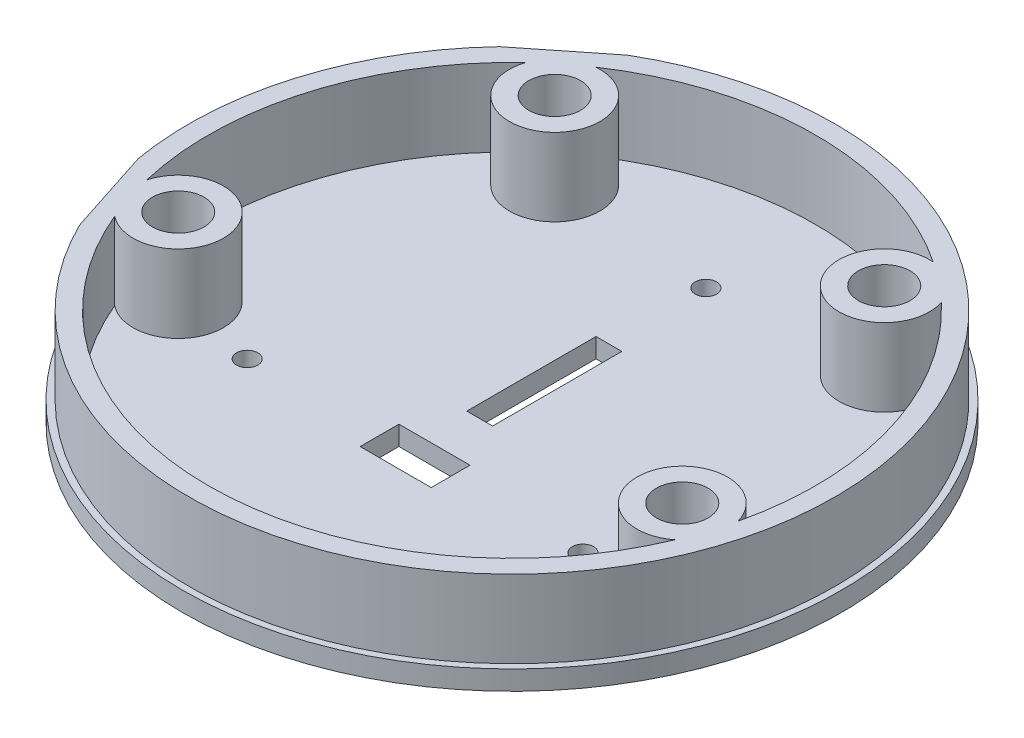
SolidWorks part; units mm, degrees
material "3.0205 (EN-AW 1200)"
ref_plane "Спереди" through (0, 0, 0) normal (0, 0, 1) x (1, 0, 0)
ref_plane "Сверху" through (0, 0, 0) normal (0, 1, 0) x (1, 0, 0)
ref_plane "Справа" through (0, 0, 0) normal (1, 0, 0) x (0, 0, -1)
other "Configuration Table"
sketch "Эскиз1" plane through (0, 0, 0) normal (0, 1, 0) x (1, 0, 0)
  circle A0 centre (0, 0) radius 51
  dimension "D1" = 102
extrude "Бобышка-Вытянуть1" add sketch "Эскиз1" along normal blind 3
sketch "Эскиз2" plane through (0, 3, 0) normal (0, 1, 0) x (1, 0, 0)
  circle A0 centre (0, 0) radius 50
  circle A1 centre (0, 0) radius 47
  circle A2 centre (0, 0) radius 51
  circle A3 centre (0, 0) radius 51
  dimension "D2" = 100
  dimension "D3" = 94
  dimension "D1" = 0
extrude "Бобышка-Вытянуть2" add sketch "Эскиз2" along normal blind 12 contours A0 A1 region at (-48.5858, 3, 0)
sketch "Эскиз5" plane through (0, 3, 0) normal (0, 1, 0) x (1, 0, 0)
  line L0 (0, 0) -> (50000, 0) construction
  line L1 (0, 0) -> (0, 50000) construction
  circle A0 centre (0, 0) radius 30 construction
  circle A1 centre (0, 30) radius 1.65
  dimension "D1" = 60
  dimension "D2" = 3.3
extrude "Вырез-Вытянуть1" cut sketch "Эскиз5" against normal blind 10
pattern_circular "Круговой массив1" count 3 over 360 about axis through (0, 15, 0) along (0, -1, 0) of "Вырез-Вытянуть1" reverse direction yes
sketch "Эскиз6" plane through (0, 3, 0) normal (0, 1, 0) x (1, 0, 0)
  line L0 (0, -1000) -> (0, 49000) construction
  line L1 (-1025.9808, -15) -> (48974.0192, -15) construction
  line L2 (-2, -5) -> (2, -5)
  line L3 (-2, -5) -> (-2, 15)
  line L4 (-2, 15) -> (2, 15)
  line L5 (2, -5) -> (2, 15)
  line L6 (-2, -5) -> (2, 15) construction
  line L7 (-2, 15) -> (2, -5) construction
  line L8 (-5.5, -12) -> (5.5, -12)
  line L9 (-5.5, -12) -> (-5.5, -18)
  line L10 (-5.5, -18) -> (5.5, -18)
  line L11 (5.5, -12) -> (5.5, -18)
  line L12 (-5.5, -12) -> (5.5, -18) construction
  line L13 (-5.5, -18) -> (5.5, -12) construction
  circle A1 centre (0, 30) radius 1.65 construction
  point P1 (0, 5)
  point P10 (0, -15)
  dimension "D3" = 15
  dimension "D1" = 4
  dimension "D2" = 20
  dimension "D4" = 6
  dimension "D5" = 11
extrude "Вырез-Вытянуть2" cut sketch "Эскиз6" against normal blind 10
sketch "Эскиз7" plane through (0, 3, 0) normal (0, 1, 0) x (1, 0, 0)
  line L0 (-1000, 0) -> (49000, 0) construction
  line L1 (0, -1000) -> (0, 49000) construction
  line L2 (-39, -12.6491) -> (39, -12.6491) construction
  line L3 (-25.5, 32.1053) -> (25.5, 32.1053) construction
  circle A0 centre (0, 0) radius 41 construction
  circle A1 centre (-39, -12.6491) radius 4
  circle A2 centre (39, -12.6491) radius 4
  circle A3 centre (-39, -12.6491) radius 7
  circle A4 centre (39, -12.6491) radius 7
  circle A5 centre (-25.5, 32.1053) radius 4
  circle A6 centre (25.5, 32.1053) radius 4
  circle A7 centre (-25.5, 32.1053) radius 7
  circle A8 centre (25.5, 32.1053) radius 7
  dimension "D1" = 82
  dimension "D2" = 8
  dimension "D3" = 8
  dimension "D5" = 14
  dimension "D6" = 14
  dimension "D7" = 8
  dimension "D8" = 8
  dimension "D10" = 14
  dimension "D11" = 14
  dimension "D4" = 78
  dimension "D9" = 51
extrude "Бобышка-Вытянуть3" add sketch "Эскиз7" along normal blind 12
sketch "Эскиз8" plane through (0, 15, 0) normal (0, 1, 0) x (1, 0, 0)
  line L0 (0, 0) -> (-39, -12.6491) construction
  line L1 (-49.2614, -8.5622) -> (-44.9093, -21.9808)
  line L2 (0, 0) -> (-25.5, 32.1053) construction
  line L3 (-36.3098, 34.3744) -> (-25.2634, 43.1481)
  circle A1 centre (0, 0) radius 50 construction
  arc A2 (-25.2634, 43.1481) -> (-36.3098, 34.3744) centre (0, 0) ccw
  arc A3 (-49.2614, -8.5622) -> (-44.9093, -21.9808) centre (0, 0) ccw
  dimension "D1" = 49.5
  dimension "D2" = 49.5
extrude "Вырез-Вытянуть3" cut sketch "Эскиз8" against normal blind 12
